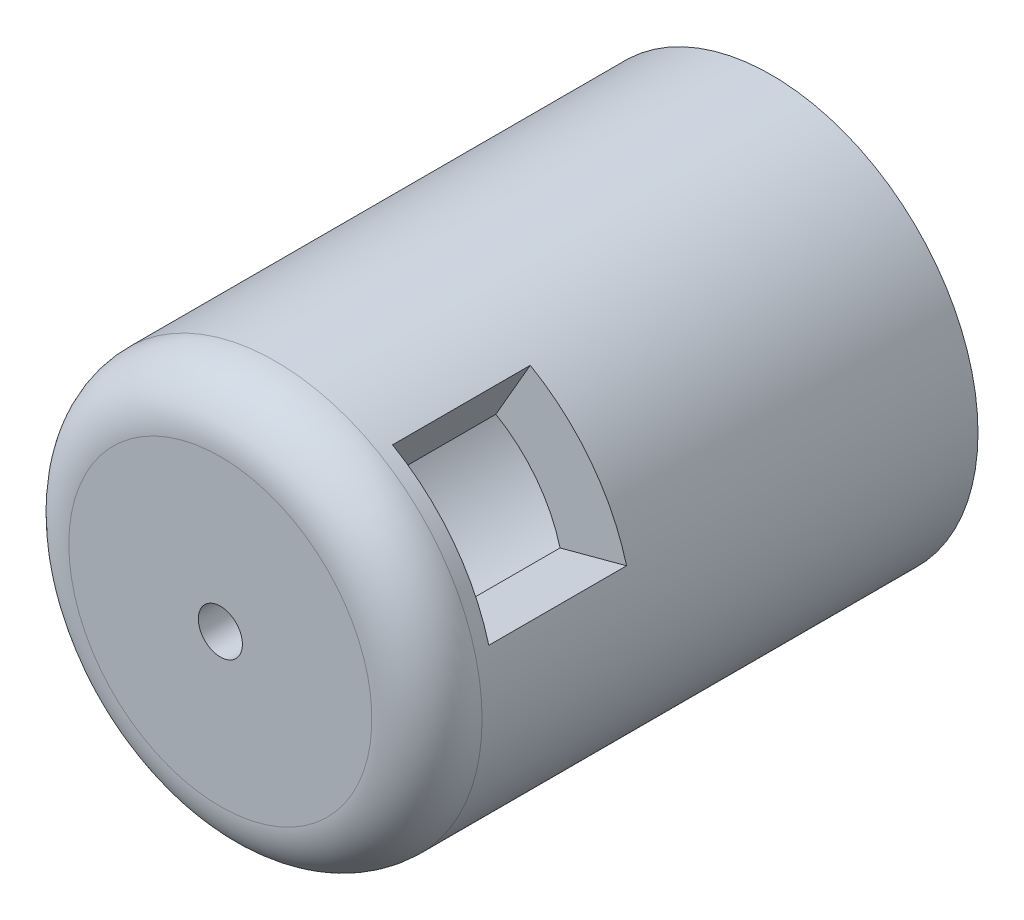
SolidWorks part; units mm, degrees
ref_plane "Front Plane" through (0, 0, 0) normal (0, 0, 1) x (1, 0, 0)
ref_plane "Top Plane" through (0, 0, 0) normal (0, 1, 0) x (1, 0, 0)
ref_plane "Right Plane" through (0, 0, 0) normal (1, 0, 0) x (0, 0, -1)
sketch "Sketch1" plane through (0, 0, 0) normal (0, 0, 1) x (1, 0, 0)
  circle A0 centre (0, 0) radius 9.525
  dimension "D1" = 19.05
extrude "Boss-Extrude1" add sketch "Sketch1" along normal blind 25.4
sketch "Sketch2" plane through (0, 0, 25.4) normal (0, 0, 1) x (1, 0, 0)
  circle A0 centre (0, 0) radius 6.35
  dimension "D1" = 12.7
extrude "Cut-Extrude1" cut sketch "Sketch2" against normal offset from surface (22.225 mm away) 3.175 up to face at (9.525, 0, 0)
ref_plane "Plane1" through (0, 0, 3.175) normal (0, 0, -1) x (-1, 0, 0)
sketch "Sketch3" plane through (0, 0, 3.175) normal (0, 0, -1) x (-1, 0, 0)
  line L0 (-9.2004, 2.4653) -> (-6.1336, 1.6435)
  line L1 (-4.7625, 8.2489) -> (-3.175, 5.4993)
  line L2 (0, 9.525) -> (0, -9.525) construction
  line L3 (6.7352, -6.7352) -> (4.4901, -4.4901)
  line L4 (0, -9.525) -> (0, -6.35)
  arc A0 (-9.2004, 2.4653) -> (-4.7625, 8.2489) centre (0, 0) cw
  circle A1 centre (0, 0) radius 9.525 construction
  arc A2 (-3.175, 5.4993) -> (-6.1336, 1.6435) centre (0, 0) ccw
  arc A3 (6.7352, -6.7352) -> (0, -9.525) centre (0, 0) cw
  arc A4 (0, -6.35) -> (4.4901, -4.4901) centre (0, 0) ccw
  dimension "D1" = 3.175
  dimension "D2" = 45
  dimension "D3" = 30
  dimension "D4" = 2
extrude "Cut-Extrude2" cut sketch "Sketch3" against normal blind 6.35
mirror "Mirror1" about plane through (0, 0, 25.4) normal (0, 0, 1) of bodies 103
delete or keep bodies "Body-Delete/Keep 1" type delete bodies bodies 103
sketch "Sketch4" plane through (0, 0, 50.8) normal (0, 0, 1) x (1, 0, 0)
  circle A0 centre (0, 0) radius 1.016
  dimension "D1" = 2.032
extrude "Cut-Extrude3" cut sketch "Sketch4" against normal up to next
fillet "Fillet1" radius 2.54 1 edges at (9.525, 0, 50.8)
